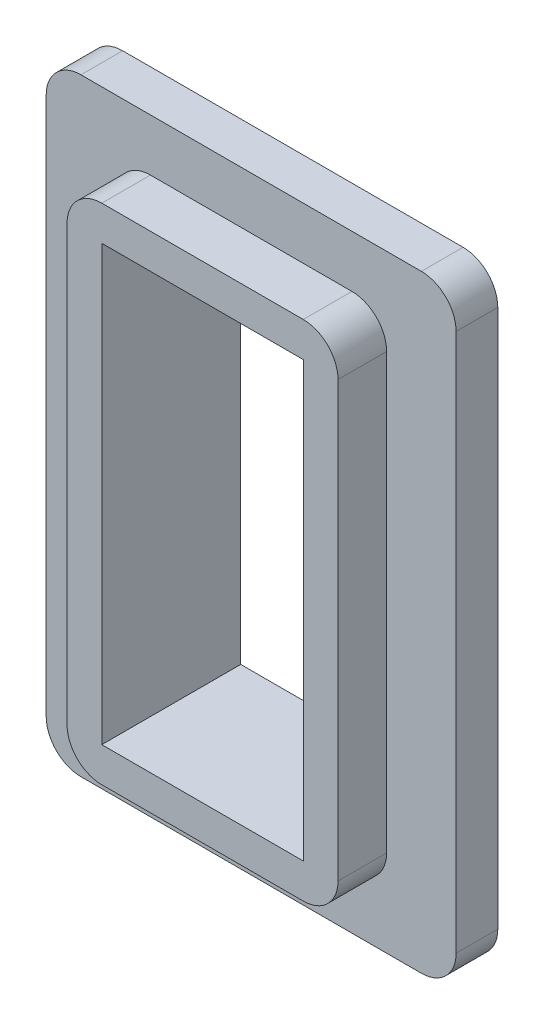
SolidWorks part; units mm, degrees
ref_plane "Top Plane" through (0, 0, 0) normal (0, 0, 1) x (1, 0, 0)
ref_plane "Front Plane" through (0, 0, 0) normal (0, 1, 0) x (1, 0, 0)
ref_plane "Right Plane" through (0, 0, 0) normal (1, 0, 0) x (0, 0, -1)
sketch "Sketch1" plane through (0, 0, 0) normal (0, 0, 1) x (1, 0, 0)
  line L6 (5.9, -8.75) -> (-5.9, -8.75)
  line L9 (-2.9, -6.25) -> (2.9, -6.25)
  line L10 (-2.9, -6.25) -> (-2.9, 6.25)
  line L11 (-2.9, 6.25) -> (2.9, 6.25)
  line L12 (2.9, -6.25) -> (2.9, 6.25)
  line L13 (-2.9, -6.25) -> (2.9, 6.25) construction
  line L14 (-2.9, 6.25) -> (2.9, -6.25) construction
  line L15 (-3.9, -7.25) -> (3.9, -7.25)
  line L16 (-3.9, -7.25) -> (-3.9, 7.25)
  line L17 (-3.9, 7.25) -> (3.9, 7.25)
  line L18 (3.9, -7.25) -> (3.9, 7.25)
  line L19 (-3.9, -7.25) -> (3.9, 7.25) construction
  line L20 (-3.9, 7.25) -> (3.9, -7.25) construction
  line L21 (5.9, -8.75) -> (5.9, 8.75)
  line L22 (5.9, 8.75) -> (-5.9, 8.75)
  line L23 (-5.9, -8.75) -> (-5.9, 8.75)
  line L24 (5.9, -8.75) -> (-5.9, 8.75) construction
  line L25 (5.9, 8.75) -> (-5.9, -8.75) construction
  point P0 (0, 0)
  point P15 (0, 0)
  point P20 (0, 0)
  dimension "D1" = 1
  dimension "D2" = 1.5
  dimension "D4" = 5.8
  dimension "D3" = 1
  dimension "D5" = 12.5
  dimension "D6" = 2
  dimension "D7" = 11.8
  dimension "D8" = 17.5
  dimension "D9" = 14.5
  dimension "D10" = 7.8
extrude "Boss-Extrude1" add sketch "Sketch1" along normal blind 0.6 and the other way blind 0.6 contours L23 L6 L21 L22 L18 L15 L16 L17 | L15 L18 L17 L16 L12 L9 L10 L11 | L9 L12 L11 L10 region at (0, -8.5389, 0) region at (0, 0, 0) region at (-3.7354, 0, 0)
extrude "Boss-Extrude2" add sketch "Sketch1<3>" along normal blind 2 and the other way blind 2 contours L11 L12 L9 L10 | L17 L18 L15 L16
sketch "Sketch1<3>" plane through (0, 0, 0) normal (0, 0, 1) x (1, 0, 0) same geometry as "Sketch1"
extrude "Cut-Extrude1" cut sketch "Sketch1<4>" against normal through all both and the other way through all contours L11 L12 L9 L10
sketch "Sketch1<4>" plane through (0, 0, 0) normal (0, 0, 1) x (1, 0, 0) same geometry as "Sketch1"
fillet "Fillet1" radius 1 12 edges at (-3.9, 7.25, -1.3) (3.9, 7.25, -1.3) (3.9, -7.25, -1.3) (-3.9, -7.25, -1.3) (-5.9, -8.75, 0) (5.9, -8.75, 0) (3.9, -7.25, 1.3) (-3.9, -7.25, 1.3) (-3.9, 7.25, 1.3) (3.9, 7.25, 1.3) (5.9, 8.75, 0) (-5.9, 8.75, 0)
